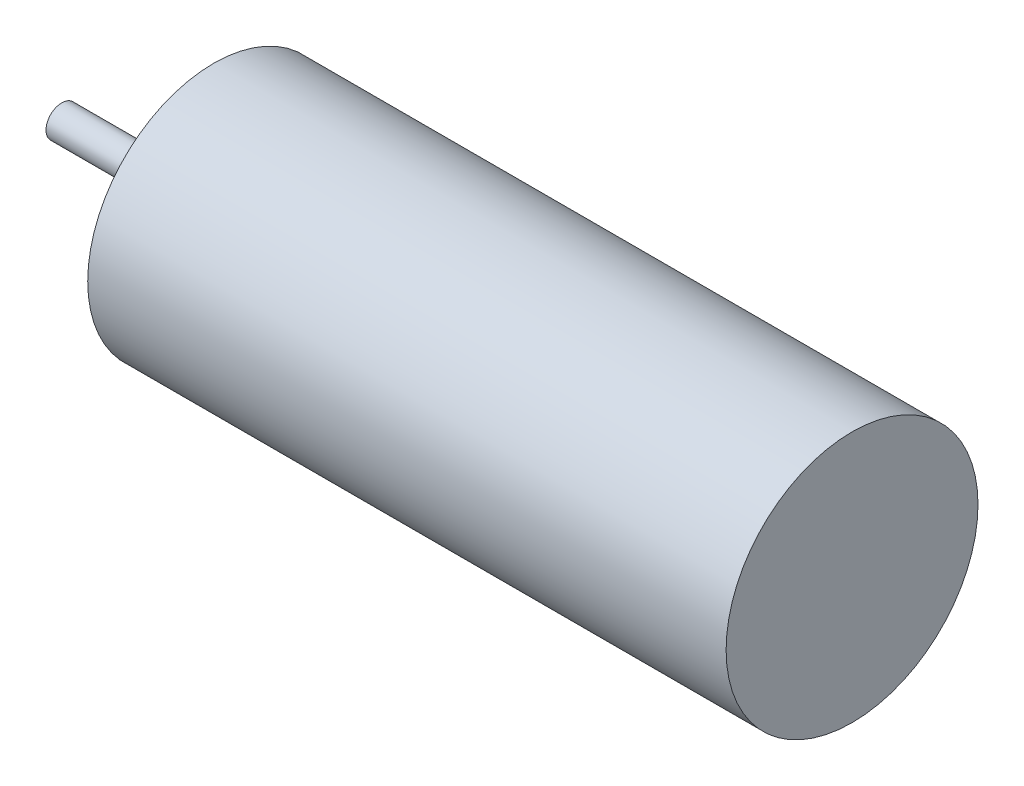
SolidWorks part; units mm, degrees
ref_plane "Front Plane" through (0, 0, 0) normal (0, 0, 1) x (1, 0, 0)
ref_plane "Top Plane" through (0, 0, 0) normal (0, 1, 0) x (1, 0, 0)
ref_plane "Right Plane" through (0, 0, 0) normal (1, 0, 0) x (0, 0, -1)
sketch "Sketch1" plane through (0, 0, 0) normal (0, 0, 1) x (1, 0, 0)
  line L0 (0, 0) -> (100.4, 0)
  line L1 (0, 0) -> (0, 2)
  line L2 (0, 2) -> (15.5, 2)
  line L3 (15.5, 2) -> (15.5, 9)
  line L4 (15.5, 9) -> (19.3, 9)
  line L5 (19.3, 9) -> (19.3, 16)
  line L6 (19.3, 16) -> (100.4, 16)
  line L7 (100.4, 16) -> (100.4, 0)
  dimension "D1" = 100.4
  dimension "D2" = 2
  dimension "D3" = 9
  dimension "D4" = 16
  dimension "D5" = 81.1
  dimension "D6" = 15.5
revolve "Revolve1" add sketch "Sketch1" angle 360 about L0
sketch "Sketch2" plane through (19.3, 0, 0) normal (-1, 0, 0) x (0, 0, 1)
  line L0 (0, 13) -> (0, -13) construction
  line L1 (-13, 0) -> (13, 0) construction
  circle A0 centre (0, 13) radius 1.5
  circle A1 centre (0, -13) radius 1.5
  circle A2 centre (-13, 0) radius 1.5
  circle A3 centre (13, 0) radius 1.5
  point P7 (0, 0)
  dimension "D1" = 26
  dimension "D2" = 3
extrude "Cut-Extrude1" cut sketch "Sketch2" against normal blind 5
